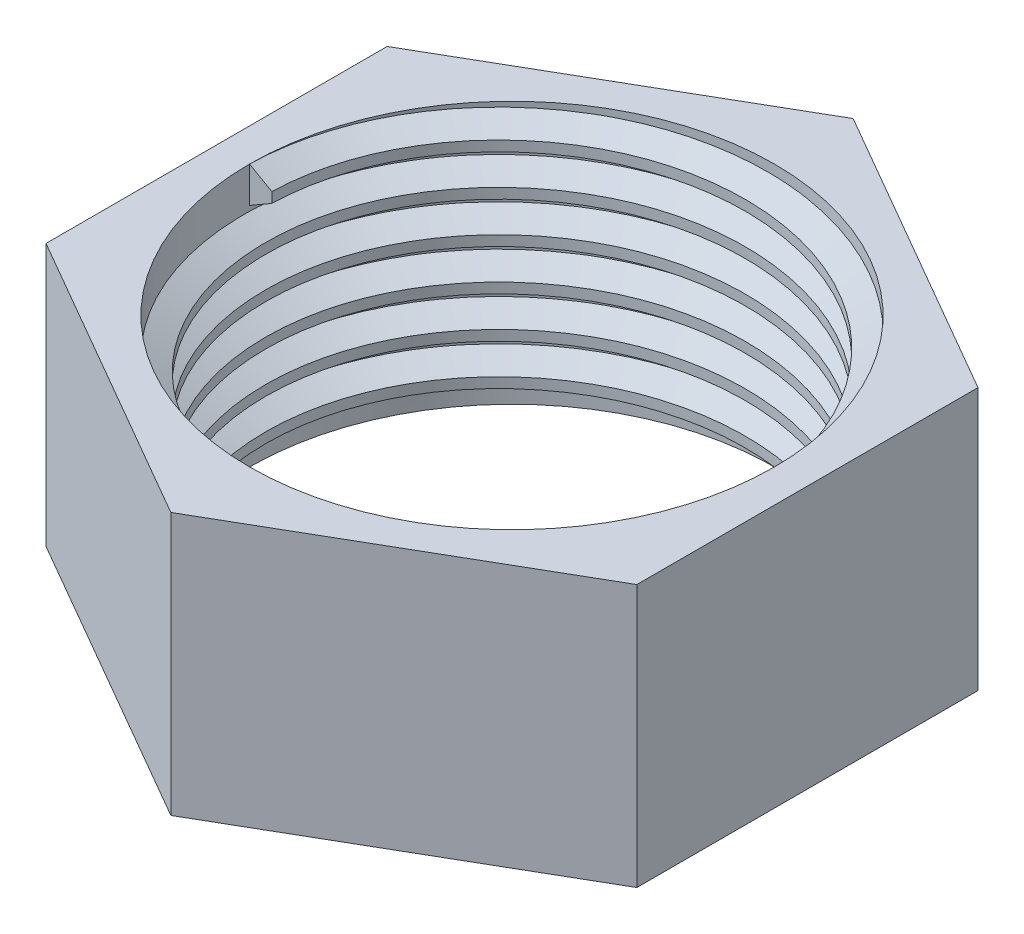
SolidWorks part; units mm, degrees
ref_plane "Front" through (0, 0, 0) normal (0, 0, 1) x (1, 0, 0)
ref_plane "Top" through (0, 0, 0) normal (0, 1, 0) x (1, 0, 0)
ref_plane "Right" through (0, 0, 0) normal (1, 0, 0) x (0, 0, -1)
sketch "Sketch2" plane through (0, 0, 0) normal (0, 1, 0) x (1, 0, 0)
  line L1 (0, 3.302) -> (-2.8596, 1.651)
  line L2 (-2.8596, 1.651) -> (-2.8596, -1.651)
  line L3 (-2.8596, -1.651) -> (0, -3.302)
  line L4 (0, -3.302) -> (2.8596, -1.651)
  line L5 (2.8596, -1.651) -> (2.8596, 1.651)
  line L6 (2.8596, 1.651) -> (0, 3.302)
  circle A0 centre (0, 0) radius 2.8596 construction
  dimension "D1" = 3.302
extrude "Boss-Extrude1" add sketch "Sketch2" along normal blind 2.54
sketch "Sketch3" plane through (0, 2.54, 0) normal (0, 1, 0) x (1, 0, 0)
  circle A0 centre (0, 0) radius 2.54
  dimension "D1" = 5.08
extrude "Cut-Extrude1" cut sketch "Sketch3" against normal through all
thread "Thread1" pitch 0.3969 method extrude profile "Thread Profile1" start angle 0, offset 0, length 2.159, pitch 0.3969, diameter 5.08
ref_plane "Plane1" through (-2.54, 2.54, 0) normal (0, 0, 1) x (-1, 0, 0)
sketch "Thread Profile1" plane through (-2.54, 2.54, 0) normal (0, 0, 1) x (-1, 0, 0)
  line L0 (0, 0) -> (0, 0.3969) construction
  line L11 (0, 0) -> (0, 0.3473)
  line L12 (0, 0.3473) -> (-0.2148, 0.2232)
  line L13 (-0.2148, 0.2232) -> (-0.2148, 0.124)
  line L15 (-0.2148, 0.124) -> (0, 0)
  line L17 (-0.2148, 0.1736) -> (0, 0.1736) construction
  point P2 (0, 0)
  dimension "Pitch" = 0.3969
  dimension "Profile_Angle" = 60
  dimension "Profile_Land" = 0.0992
  dimension "Profile_Height" = 0.2148
